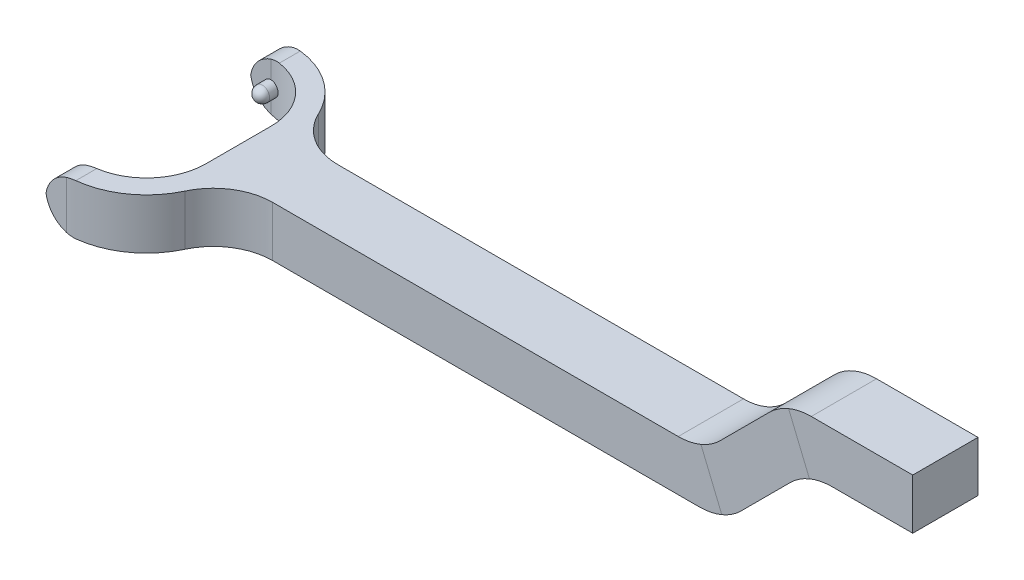
SolidWorks part; units mm, degrees
ref_plane "Front Plane" through (0, 0, 0) normal (0, 0, 1) x (1, 0, 0)
ref_plane "Top Plane" through (0, 0, 0) normal (0, 1, 0) x (1, 0, 0)
ref_plane "Right Plane" through (0, 0, 0) normal (1, 0, 0) x (0, 0, -1)
sketch "Sketch1" plane through (0, 0, 0) normal (1, 0, 0) x (0, 0, -1)
  line L1 (0, 0) -> (11, 0)
  line L2 (0, 0) -> (0, -8.5)
  line L3 (0, -8.5) -> (11, -8.5)
  line L4 (11, 0) -> (11, -8.5)
  dimension "D1" = 11
  dimension "D2" = 8.5
extrude "Boss-Extrude1" add sketch "Sketch1" along normal blind 75
ref_plane "Plane2" through (0, -4.25, 0) normal (0, 1, 0) x (1, 0, 0)
sketch3d "3DSketch3"
  line L0 (75, -3, -5.5) -> (85, -3, -5.5)
  line L1 (85, -3, -5.5) -> (99.1421, 11.1421, -5.5)
  line L2 (75, 0, -11) -> (75, 0, 0) construction
  line L3 (75, -8.5, -11) -> (75, 0, -11) construction
  line L4 (99.1421, 11.1421, -5.5) -> (119.1421, 11.1421, -5.5)
  dimension "D1" = 3
  dimension "D2" = 0
  dimension "D3" = 5.5
  dimension "D4" = 135
  dimension "D5" = 10
  dimension "D6" = 20
  dimension "D7" = 20
sketch "Sketch14" plane through (75, 0, 0) normal (1, 0, 0) x (0, 0, -1)
  line L1 (0, 0) -> (11, 0)
  line L2 (0, 0) -> (0, -8.5)
  line L3 (0, -8.5) -> (11, -8.5)
  line L4 (11, 0) -> (11, -8.5)
sweep "Sweep3" add profiles "Sketch14" path "3DSketch3"
fillet "Fillet1" radius 10 4 edges at (87.2782, -8.5, -5.5) (101.4203, 5.6421, -5.5) (97.8995, 14.1421, -5.5) (83.7574, 0, -5.5)
sketch "Sketch17" plane through (0, 0, 0) normal (0, 1, 0) x (1, 0, 0)
  line L0 (-10, -10) -> (-13.5, -10)
  line L1 (-13.5, -10) -> (-13.5, -13.5)
  line L2 (-13.5, -13.5) -> (-10, -13.5)
  line L4 (-23.4629, 5.5) -> (20.4079, 5.5) construction
  line L5 (79.6152, 0) -> (0, 0) construction
  line L20 (3.5, 0) -> (3.5, 11)
  line L22 (-13.5, 24.5) -> (-10, 24.5)
  line L23 (0, 0) -> (0, 11)
  line L24 (-13.5, 21) -> (-13.5, 24.5)
  line L25 (-10, 21) -> (-13.5, 21)
  arc A0 (-10, -10) -> (0, 0) centre (-10, 0) ccw
  arc A2 (-10, -13.5) -> (3.5, 0) centre (-10, 0) ccw
  arc A3 (-10, 24.5) -> (3.5, 11) centre (-10, 11) cw
  arc A4 (-10, 21) -> (0, 11) centre (-10, 11) cw
  dimension "D3" = 20
  dimension "D6" = 3.5
  dimension "D1" = 0
  dimension "D2" = 10
  dimension "D5" = 3.5
  dimension "D7" = 5.5
extrude "Boss-Extrude3" add sketch "Sketch17" along normal blind 8.5 from offset 8.5 offset against normal yes
fillet "Fillet5" radius 10 2 edges at (3.5, -4.25, 0) (3.5, -4.25, -11)
fillet "Fillet6" radius 5 4 edges at (-13.5, 0, 11.75) (-13.5, -8.5, 11.75) (-13.5, -8.5, -22.75) (-13.5, 0, -22.75)
sketch "Sketch18" plane through (0, 0, -21) normal (0, 0, 1) x (1, 0, 0)
  line L1 (-8.5, -8.5) -> (0, -8.5) construction
  line L2 (-10, -0.2303) -> (-10, -8.2697) construction
  circle A0 centre (-10, -4.5) radius 1.25
  dimension "D1" = 2.5
  dimension "D2" = 0
  dimension "D3" = 4
extrude "Boss-Extrude4" add sketch "Sketch18" along normal blind 1.5
sketch "Sketch19" plane through (0, 0, 10) normal (0, 0, -1) x (-1, 0, 0)
  line L0 (10, -0.2303) -> (10, -8.2697) construction
  circle A0 centre (10, -4.5) radius 1.25
  dimension "D1" = 2.5
  dimension "D2" = 4
extrude "Boss-Extrude5" add sketch "Sketch19" along normal blind 1.5
ref_plane "CenterOfClips" through (-7.5, 0, 0) normal (-1, 0, 0) x (0, 0, 1)
sketch "Sketch24" plane through (0, 0, 8.5) normal (0, 0, -1) x (-1, 0, 0)
  line L0 (10, -3.25) -> (10, -5.75)
  circle A0 centre (10, -4.5) radius 1.25 construction
  arc A1 (10, -5.75) -> (10, -3.25) centre (10, -4.5) ccw
revolve "Revolve9" add sketch "Sketch24" angle 180 about L0
sketch "Sketch25" plane through (0, 0, -19.5) normal (0, 0, 1) x (1, 0, 0)
  line L0 (-10, -3.25) -> (-10, -5.75)
  circle A0 centre (-10, -4.5) radius 1.25 construction
  arc A1 (-10, -3.25) -> (-10, -5.75) centre (-10, -4.5) ccw
revolve "Revolve10" add sketch "Sketch25" angle 180 about L0 reverse direction yes
